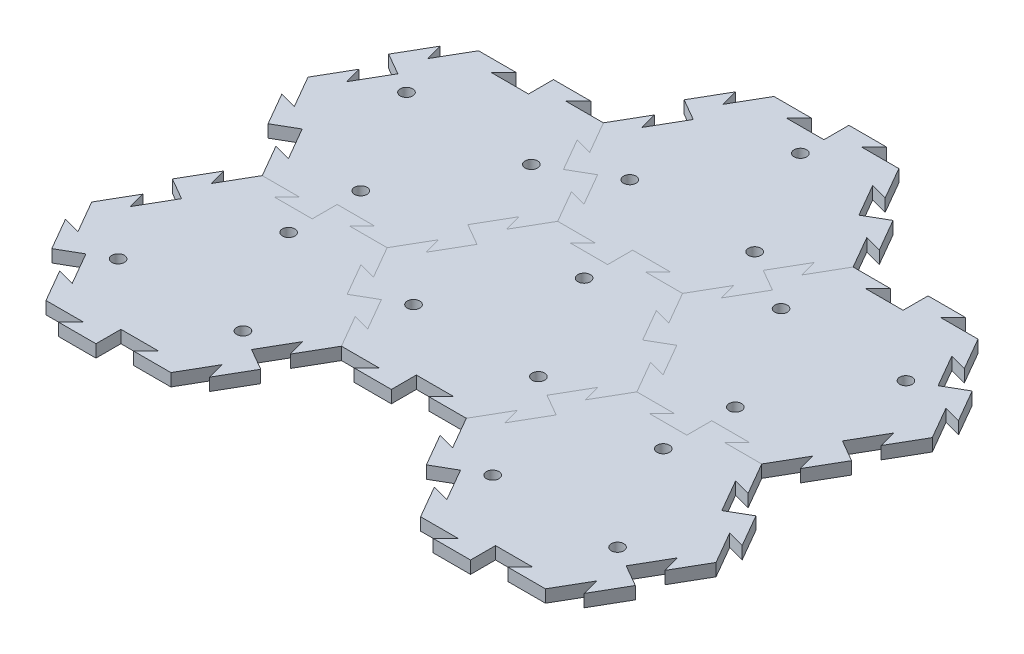
SolidWorks part; units mm, degrees
note: '?' marks a value the reader was unsure of.
material "Cedar"
ref_plane "Front Plane" through (0, 0, 0) normal (0, 0, 1) x (1, 0, 0)
ref_plane "Top Plane" through (0, 0, 0) normal (0, 1, 0) x (1, 0, 0)
ref_plane "Right Plane" through (0, 0, 0) normal (1, 0, 0) x (0, 0, -1)
sketch "Sketch1" plane through (0, 0, 0) normal (0, 1, 0) x (1, 0, 0)
  line L0 (0, 0) -> (63.5, 0) construction
  line L1 (63.5, 0) -> (31.75, 54.9926)
  line L2 (31.75, 54.9926) -> (-31.75, 54.9926)
  line L3 (-31.75, 54.9926) -> (-63.5, 0)
  line L4 (-63.5, 0) -> (-31.75, -54.9926)
  line L5 (-31.75, -54.9926) -> (31.75, -54.9926)
  line L6 (31.75, -54.9926) -> (63.5, 0)
  circle A0 centre (0, 0) radius 54.9926 construction
  dimension "D1" = 63.5
extrude "Boss-Extrude1" add sketch "Sketch1" against normal blind 6.35
sketch "Sketch2" plane through (0, 0, 0) normal (0, 1, 0) x (1, 0, 0)
  point P1 (0, 0)
ref_axis "Axis1" through (0, 0, 0) along (0, 1, 0)?
sketch "Sketch9" plane through (0, 0, 0) normal (0, 1, 0) x (1, 0, 0)
  line L1 (31.75, -18.3309) -> (0, 36.6617) construction
  line L2 (0, 36.6617) -> (-31.75, -18.3309) construction
  line L3 (-31.75, -18.3309) -> (31.75, -18.3309) construction
  circle A0 centre (0, 0) radius 18.3309 construction
  circle A1 centre (-31.75, -18.3309) radius 3.175
  dimension "D2" = 6.35
  dimension "D1" = 63.5
extrude "Cut-Extrude3" cut sketch "Sketch9" against normal through all
pattern_circular "CirPattern6" count 3 over 360 about axis through (0, 0, 0) along (0, 1, 0) of "Cut-Extrude3"
sketch "Sketch10" plane through (0, 0, 0) normal (0, 1, 0) x (1, 0, 0)
  line L0 (31.75, 54.9926) -> (41.275, 38.4948) construction
  line L1 (41.275, 38.4948) -> (32.6007, 40.8191)
  line L2 (32.6007, 40.8191) -> (42.1257, 24.3213)
  line L3 (42.1257, 24.3213) -> (47.625, 27.4963)
  line L4 (41.275, 38.4948) -> (47.625, 27.4963)
  line L5 (63.5, 0) -> (31.75, 54.9926) construction
  dimension "D1" = 45
  dimension "D2" = 6.35
extrude "Cut-Extrude4" cut sketch "Sketch10" against normal through all
sketch "Sketch11" plane through (0, 0, 0) normal (0, 1, 0) x (1, 0, 0)
  line L0 (47.625, 27.4963) -> (63.5, 0) construction
  line L1 (47.625, 27.4963) -> (53.1243, 30.6713)
  line L2 (53.1243, 30.6713) -> (62.6493, 14.1735)
  line L3 (62.6493, 14.1735) -> (53.975, 16.4978)
  line L4 (53.975, 16.4978) -> (47.625, 27.4963)
  line L5 (53.975, 16.4978) -> (63.5, 0) construction
  line L6 (53.975, 16.4978) -> (63.5, 0) construction
  line L7 (63.5, 0) -> (47.625, 27.4963) construction
  line L8 (31.75, -54.9926) -> (63.5, 0) construction
  dimension "D1" = 45
  dimension "D2" = 6.35
extrude "Boss-Extrude4" add sketch "Sketch11" against normal blind 6.35 contours L1 L2 L3 L4
pattern_circular "CirPattern7" count 6 over 360 about axis through (0, 0, 0) along (0, 1, 0) of "Cut-Extrude4", "Boss-Extrude4"
pattern_linear "LPattern1" count 2 spacing 109.9852 along (0.866, 0, 0.5) of bodies 125
pattern_circular "CirPattern8" count 5 every 60 about axis through (0, 0, 0) along (0, 1, 0) of bodies 130
